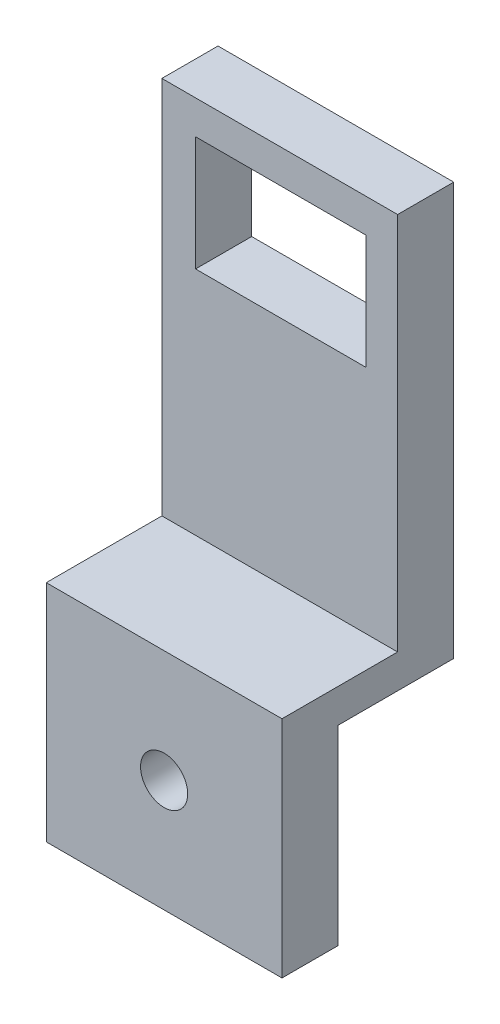
SolidWorks part; units mm, degrees
ref_plane "Front Plane" through (0, 0, 0) normal (0, 0, 1) x (1, 0, 0)
ref_plane "Top Plane" through (0, 0, 0) normal (0, 1, 0) x (1, 0, 0)
ref_plane "Right Plane" through (0, 0, 0) normal (1, 0, 0) x (0, 0, -1)
sketch "Sketch1" plane through (0, 0, 0) normal (0, 0, 1) x (1, 0, 0)
  line L1 (0, 0) -> (21, 0)
  line L2 (0, 0) -> (0, 53.75)
  line L3 (0, 53.75) -> (21, 53.75)
  line L4 (21, 0) -> (21, 53.75)
  line L5 (3, 50.75) -> (18.2, 50.75)
  line L6 (3, 50.75) -> (3, 40.55)
  line L7 (3, 40.55) -> (18.2, 40.55)
  line L8 (18.2, 50.75) -> (18.2, 40.55)
  circle A1 centre (10.5, 10) radius 2.1
  dimension "D6" = 4.2
  dimension "D9" = 10.5
  dimension "D1" = 10.2
  dimension "D2" = 15.2
  dimension "D3" = 21
  dimension "D4" = 3
  dimension "D5" = 3
  dimension "D7" = 10
  dimension "D11" = 40.55
extrude "Boss-Extrude1" add sketch "Sketch1" along normal blind 15.3
sketch "Sketch2" plane through (0, 0, 0) normal (-1, 0, 0) x (0, 0, 1)
  line L0 (15.3, 53.75) -> (0, 53.75) construction
  line L1 (15.3, 53.75) -> (5, 53.75)
  line L2 (15.3, 53.75) -> (15.3, 20)
  line L3 (15.3, 20) -> (5, 20)
  line L4 (5, 53.75) -> (5, 20)
  line L5 (15.3, 53.75) -> (15.3, 0) construction
  line L6 (0, 53.75) -> (0, 0) construction
  line L7 (0, 0) -> (10.3, 0)
  line L8 (0, 0) -> (0, 17)
  line L9 (0, 17) -> (10.3, 17)
  line L10 (10.3, 0) -> (10.3, 17)
  dimension "D1" = 17
  dimension "D2" = 3
  dimension "D3" = 5
  dimension "D4" = 5
extrude "Cut-Extrude1" cut sketch "Sketch2" against normal blind 21 contours L2 L1 L4 L3 | L8 L7 L10 L9
